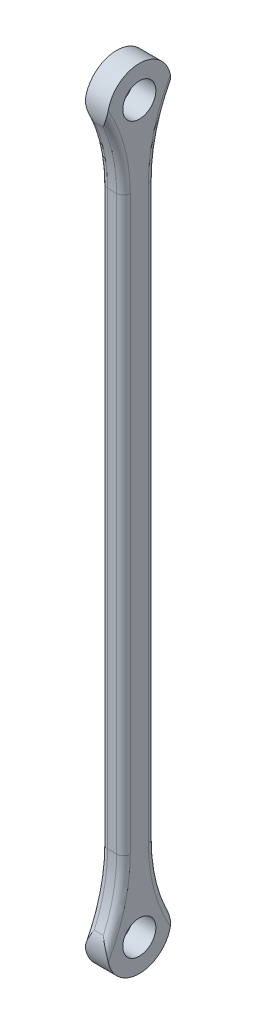
SolidWorks part; units mm, degrees
ref_plane "Alzado" through (0, 0, 0) normal (0, 0, 1) x (1, 0, 0)
ref_plane "Planta" through (0, 0, 0) normal (0, 1, 0) x (1, 0, 0)
ref_plane "Vista lateral" through (0, 0, 0) normal (1, 0, 0) x (0, 0, -1)
sketch "Croquis1" plane through (-25.8696, 0, 0) normal (-1, 0, 0) x (0, 0, 1)
  circle A0 centre (65.25, 31.0637) radius 4
  circle A1 centre (65.25, 31.0637) radius 6.5
sketch "Croquis2" plane through (-23.6696, 0, 0) normal (-1, 0, 0) x (0, 0, 1)
  circle A1 centre (65.25, 31.0637) radius 7
  dimension "D1" = 14
extrude "Saliente-Extruir2" add sketch "Croquis2" along normal blind 5
sketch "Croquis5" plane through (-23.6696, 0, 0) normal (1, 0, 0) x (0, 0, -1)
  line L0 (-65.25, 31.0637) -> (-65.25, 191.0637) construction
  line L1 (-61.75, 174.2011) -> (-61.75, 47.9262)
  line L2 (-61.75, 111.0637) -> (-2.8211, 111.0637) construction
  line L3 (-68.75, 174.2011) -> (-68.75, 47.9262)
  arc A0 (-58.8282, 188.2778) -> (-71.6718, 188.2778) centre (-65.25, 191.0637) ccw
  arc A2 (-58.8282, 188.2778) -> (-61.75, 174.2011) centre (-26.3792, 174.2011) ccw
  arc A3 (-58.8282, 33.8495) -> (-61.75, 47.9262) centre (-26.3792, 47.9262) cw
  arc A4 (-71.6718, 33.8495) -> (-68.75, 47.9262) centre (-104.1208, 47.9262) ccw
  arc A5 (-71.6718, 188.2778) -> (-68.75, 174.2011) centre (-104.1208, 174.2011) cw
  arc A6 (-58.8282, 33.8495) -> (-71.6718, 33.8495) centre (-65.25, 31.0637) ccw
  dimension "D3" = 7
  dimension "D1" = 160
  dimension "D2" = 3.5
extrude "Saliente-Extruir3" add sketch "Croquis5" against normal blind 5
sketch "Croquis8" plane through (-28.6696, 0, 0) normal (-1, 0, 0) x (0, 0, 1)
  circle A0 centre (65.25, 191.0637) radius 3.65
  arc A3 (71.6718, 188.2778) -> (58.8282, 188.2778) centre (65.25, 191.0637) ccw construction
  dimension "D1" = 7.3
extrude "Cortar-Extruir4" cut sketch "Croquis8" against normal blind 11
sketch "Croquis10" plane through (-28.6696, 0, 0) normal (-1, 0, 0) x (0, 0, 1)
  circle A0 centre (65.25, 31.0637) radius 3.65
  dimension "D1" = 7.3
extrude "Cortar-Extruir7" cut sketch "Croquis10" against normal blind 7
fillet "Redondeo8" radius 1.5 12 edges at (-23.6696, 111.0637, 68.75) (-28.6696, 111.0637, 68.75) (-23.6696, 111.0637, 61.75) (-28.6696, 111.0637, 61.75) (-23.6696, 40.7378, 69.4881) (-28.6696, 40.7378, 69.4881) (-23.6696, 40.7378, 61.0119) (-28.6696, 40.7378, 61.0119) (-23.6696, 181.3895, 69.4881) (-28.6696, 181.3895, 69.4881) (-23.6696, 181.3895, 61.0119) (-28.6696, 181.3895, 61.0119)
